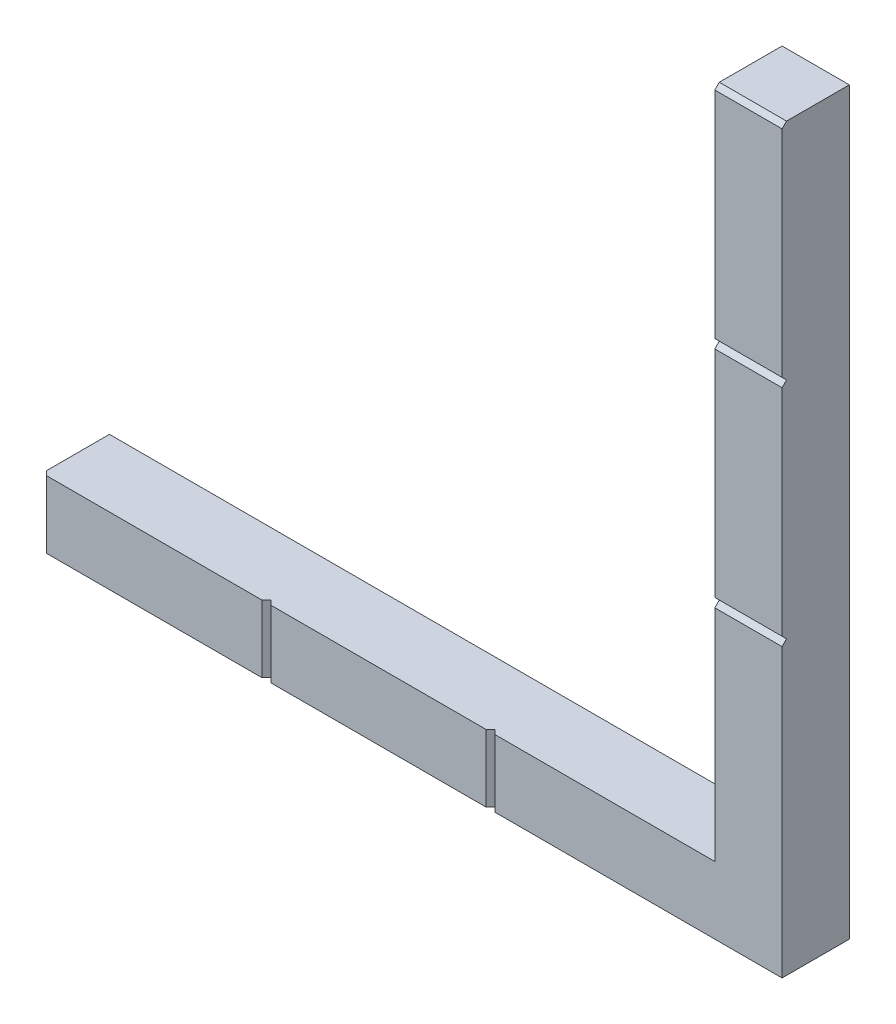
SolidWorks part; units mm, degrees
ref_plane "Front Plane" through (0, 0, 0) normal (0, 0, 1) x (1, 0, 0)
ref_plane "Top Plane" through (0, 0, 0) normal (0, 1, 0) x (1, 0, 0)
ref_plane "Right Plane" through (0, 0, 0) normal (1, 0, 0) x (0, 0, -1)
sketch "Sketch1" plane through (0, 0, 0) normal (0, 0, 1) x (1, 0, 0)
  line L0 (0, 0) -> (0, 150)
  line L1 (0, 150) -> (15, 150)
  line L2 (15, 150) -> (15, -15)
  line L3 (15, -15) -> (-150, -15)
  line L4 (-150, -15) -> (-150, 0)
  line L5 (-150, 0) -> (0, 0)
  dimension "D1" = 15
  dimension "D2" = 15
  dimension "D3" = 150
  dimension "D4" = 150
extrude "Boss-Extrude1" add sketch "Sketch1" along normal blind 15
sketch "Sketch3" plane through (0, 0, 15) normal (0, 0, 1) x (1, 0, 0)
  line L0 (-150, -7.5) -> (15, -7.5) construction
  line L1 (-150, 0) -> (-150, -15) construction
  line L2 (15, -15) -> (15, 150) construction
  line L3 (7.5, 150) -> (7.5, -15) construction
  line L4 (15, 150) -> (0, 150) construction
  line L5 (-150, -15) -> (15, -15) construction
  line L6 (0, 0) -> (-150, 0) construction
  line L7 (-51, -15) -> (-49, -15)
  line L8 (-51, -15) -> (-51, 0)
  line L9 (-51, 0) -> (-49, 0)
  line L10 (-49, -15) -> (-49, 0)
  line L11 (-51, -15) -> (-49, 0) construction
  line L12 (-51, 0) -> (-49, -15) construction
  line L13 (0, 150) -> (0, 0) construction
  line L15 (-101, -15) -> (-99, -15)
  line L16 (-101, -15) -> (-101, 0)
  line L17 (-101, 0) -> (-99, 0)
  line L18 (-99, -15) -> (-99, 0)
  line L19 (-101, -15) -> (-99, 0) construction
  line L20 (-101, 0) -> (-99, -15) construction
  line L27 (0, 51) -> (15, 51)
  line L28 (0, 51) -> (0, 49)
  line L29 (0, 49) -> (15, 49)
  line L30 (15, 51) -> (15, 49)
  line L31 (0, 51) -> (15, 49) construction
  line L32 (0, 49) -> (15, 51) construction
  line L33 (0, 101) -> (15, 101)
  line L34 (0, 101) -> (0, 99)
  line L35 (0, 99) -> (15, 99)
  line L36 (15, 101) -> (15, 99)
  line L37 (0, 101) -> (15, 99) construction
  line L38 (0, 99) -> (15, 101) construction
  point P12 (-50, -7.5)
  point P21 (-100, -7.5)
  point P30 (7.5, 50)
  point P35 (7.5, 100)
  dimension "D1" = 2
  dimension "D2" = 50
  dimension "D3" = 100
  dimension "D5" = 2
  dimension "D7" = 2
  dimension "D8" = 100
  dimension "D9" = 50
  dimension "D10" = 2
extrude "Cut-Extrude2" cut sketch "Sketch3" against normal blind 2
fillet "Fillet1" radius 2 8 edges at (-101, -7.5, 13) (-99, -7.5, 13) (-51, -7.5, 13) (-49, -7.5, 13) (7.5, 49, 13) (7.5, 51, 13) (7.5, 101, 13) (7.5, 99, 13) profile chamfer
sketch "Sketch4" plane through (0, -15, 0) normal (0, -1, 0) x (1, 0, 0)
  line L0 (-150, 15) -> (-150, 14)
  line L1 (-150, 15) -> (-150, 0) construction
  line L2 (-150, 14) -> (-149, 15)
  line L3 (-150, 15) -> (-101, 15) construction
  line L4 (-149, 15) -> (-150, 15)
  dimension "D1" = 1
  dimension "D2" = 1
extrude "Cut-Extrude3" cut sketch "Sketch4" against normal through all both and the other way through all
sketch "Sketch5" plane through (15, 0, 0) normal (1, 0, 0) x (0, 0, -1)
  line L0 (-15, 150) -> (-15, 149)
  line L1 (-15, 101) -> (-15, 150) construction
  line L2 (-15, 149) -> (-14, 150)
  line L3 (-15, 150) -> (0, 150) construction
  line L4 (-14, 150) -> (-15, 150)
  dimension "D1" = 1
  dimension "D2" = 1
extrude "Cut-Extrude4" cut sketch "Sketch5" against normal through all both and the other way through all
sketch "Sketch7" plane through (0, 0, 0) normal (-1, 0, 0) x (0, 0, 1)
  line L0 (5.75, 150) -> (5.75, -15) construction
  line L3 (14, 150) -> (0, 150) construction
  line L4 (14, -15) -> (0, -15) construction
  line L5 (0, 150) -> (0, 0) construction
  circle A0 centre (5.75, 75) radius 2.6
  circle A1 centre (5.75, 125) radius 2.6
  circle A2 centre (5.75, 25) radius 2.6
  dimension "D2" = 5.2
  dimension "D4" = 5.2
  dimension "D6" = 5.2
  dimension "D1" = 25
  dimension "D3" = 25
  dimension "D5" = 25
  dimension "D7" = 5.75
  dimension "D8" = 0
  dimension "D9" = 0
  dimension "D10" = 0
extrude "Cut-Extrude5" cut sketch "Sketch7" against normal blind 8
